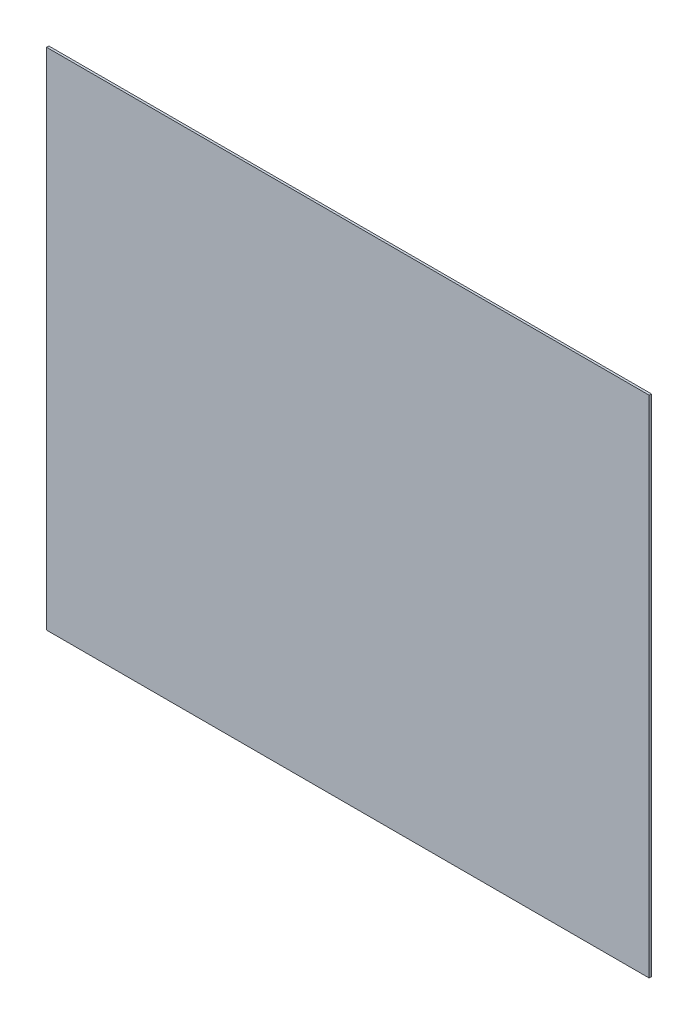
SolidWorks part; units mm, degrees
material "Mahogany"
ref_plane "Front Plane" through (0, 0, 0) normal (0, 0, 1) x (1, 0, 0)
ref_plane "Top Plane" through (0, 0, 0) normal (0, 1, 0) x (1, 0, 0)
ref_plane "Right Plane" through (0, 0, 0) normal (1, 0, 0) x (0, 0, -1)
sketch "Sketch1" plane through (0, 0, 0) normal (0, 0, 1) x (1, 0, 0)
  line L1 (-422.5, -354) -> (422.5, -354)
  line L2 (-422.5, -354) -> (-422.5, 354)
  line L3 (-422.5, 354) -> (422.5, 354)
  line L4 (422.5, -354) -> (422.5, 354)
  line L5 (-422.5, -354) -> (422.5, 354) construction
  line L6 (-422.5, 354) -> (422.5, -354) construction
  point P0 (0, 0)
  dimension "D1" = 845
  dimension "D2" = 708
extrude "Boss-Extrude1" add sketch "Sketch1" along normal blind 3.175
equation "\"W\"= 1750"
equation "\"L\"= 780"
equation "\"H\"= 780"
equation "\"ARM_BOLT_SPACING\"= 166"
equation "\"ARM_TO_WALL\"= 200"
equation "\"D1@Sketch1\"=(\"W\"/2)-30"
equation "\"D2@Sketch1\"=\"H\"-72"
